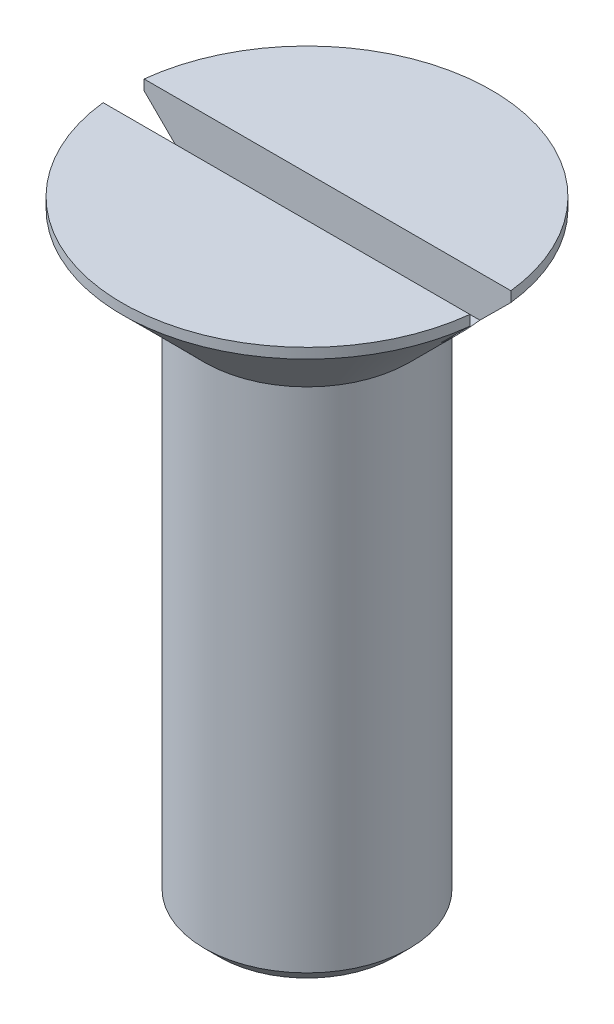
SolidWorks part; units mm, degrees
ref_plane "Спереди" through (0, 0, 0) normal (0, 0, 1) x (1, 0, 0)
ref_plane "Сверху" through (0, 0, 0) normal (0, 1, 0) x (1, 0, 0)
ref_plane "Справа" through (0, 0, 0) normal (1, 0, 0) x (0, 0, -1)
sketch "Эскиз1" plane through (0, 0, 0) normal (0, 0, 1) x (1, 0, 0)
  line L0 (0, 125.7632) -> (0, 0) construction
  line L2 (0, 30) -> (0, 0)
  line L3 (0, 30) -> (9, 30)
  line L4 (5, 25.5) -> (5, 0)
  line L5 (5, 25.5) -> (9, 29.5)
  line L6 (5, 0) -> (0, 0)
  line L7 (9, 30) -> (9, 29.5)
  dimension "D1" = 9
  dimension "D2" = 30
  dimension "D3" = 4.5
  dimension "D4" = 45
  dimension "D5" = 5
revolve "Повернуть1" add sketch "Эскиз1" angle 360 about L0
ref_axis "Ось4" through (0, 18.7854, 0) along (0, -1, 0)
sketch "Эскиз13" plane through (0, 30, 0) normal (0, 1, 0) x (-1, 0, 0)
  line L1 (9.5, -1) -> (-9.5, -1)
  line L2 (9.5, -1) -> (9.5, 1)
  line L3 (9.5, 1) -> (-9.5, 1)
  line L4 (-9.5, -1) -> (-9.5, 1)
  dimension "D1" = 9.5
  dimension "D2" = 19
  dimension "D3" = 1
  dimension "D4" = 2
extrude "Вырез-Вытянуть9" cut sketch "Эскиз13" against normal blind 2
chamfer "Фаска1" distance 0.75 angle 45 1 edges at (-5, 0, 0)
